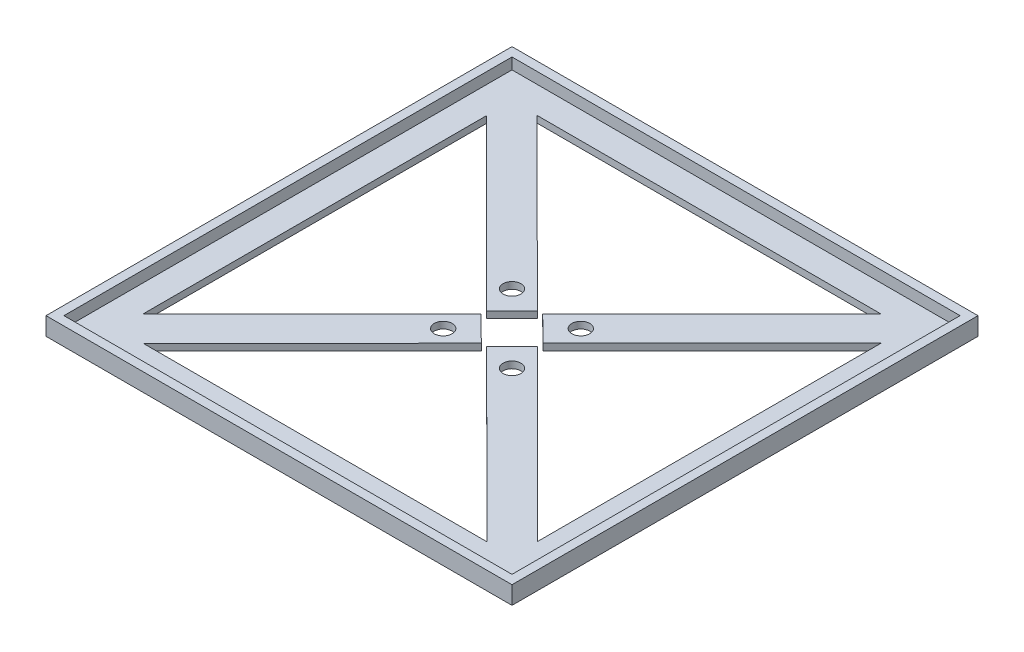
SolidWorks part; units mm, degrees
ref_plane "Front Plane" through (0, 0, 0) normal (0, 0, 1) x (1, 0, 0)
ref_plane "Top Plane" through (0, 0, 0) normal (0, 1, 0) x (1, 0, 0)
ref_plane "Right Plane" through (0, 0, 0) normal (1, 0, 0) x (0, 0, -1)
sketch "Sketch1" plane through (0, 0, 0) normal (0, 1, 0) x (1, 0, 0)
  line L0 (-31.2989, 24.3007) -> (-9.4284, 2.4649)
  line L1 (-31.2989, 27.1639) -> (18.7011, 27.1639)
  line L2 (-31.2989, 27.1639) -> (-31.2989, -22.8361)
  line L3 (-31.2989, -22.8361) -> (18.7011, -22.8361)
  line L4 (18.7011, 27.1639) -> (18.7011, -22.8361)
  line L5 (-31.2989, 27.1639) -> (18.7011, -22.8361) construction
  line L6 (-31.2989, -22.8361) -> (18.7011, 27.1639) construction
  line L7 (-9.4284, 2.4649) -> (-6.6022, 5.2956)
  line L8 (-6.6022, 5.2956) -> (-28.5053, 27.1639)
  line L9 (15.8379, 27.1639) -> (-5.9979, 5.2933)
  line L10 (-3.1672, 2.4672) -> (18.7011, 24.3702)
  line L11 (-5.9979, 5.2933) -> (-3.1672, 2.4672)
  line L12 (18.7011, -19.973) -> (-3.1695, 1.8628)
  line L13 (-5.9957, -0.9679) -> (15.9074, -22.8361)
  line L14 (-3.1695, 1.8628) -> (-5.9957, -0.9679)
  line L15 (-28.4358, -22.8361) -> (-6.6, -0.9656)
  line L16 (-9.4307, 1.8606) -> (-31.2989, -20.0425)
  line L17 (-6.6, -0.9656) -> (-9.4307, 1.8606)
  circle A0 centre (-10.1366, 6.0016) radius 1
  circle A1 centre (-2.4612, 6.0016) radius 1
  circle A2 centre (-2.4612, -1.6738) radius 1
  circle A3 centre (-10.1366, -1.6738) radius 1
  point P5 (-8.0153, 3.8802)
  point P11 (-6.2989, 2.1639)
  point P33 (-6.2989, 2.1639)
  dimension "D3" = 2
  dimension "D4" = 3
  dimension "D1" = 50
  dimension "D2" = 50
  dimension "D5" = 4
  dimension "D6" = 4
extrude "Extrude-Thin1" add sketch "Sketch1" along normal blind 0.75 thin contours L2 L3 L4 L1 thin type one direction reverse wall 3
extrude "Boss-Extrude1" add sketch "Sketch1<3>" along normal blind 0.75 contours L15 L17 L16 L2 L3 A3 | L12 L14 L13 L3 L4 A2 | L9 L11 L10 L4 L1 A1 | L7 L8 L1 L2 L0 A0
sketch "Sketch1<3>" plane through (0, 0, 0) normal (0, 1, 0) x (1, 0, 0) same geometry as "Sketch1"
extrude "Extrude-Thin2" add sketch "Sketch1<4>" along normal blind 2 thin contours L2 L3 L4 L1 thin type one direction wall 1
sketch "Sketch1<4>" plane through (0, 0, 0) normal (0, 1, 0) x (1, 0, 0) same geometry as "Sketch1"
